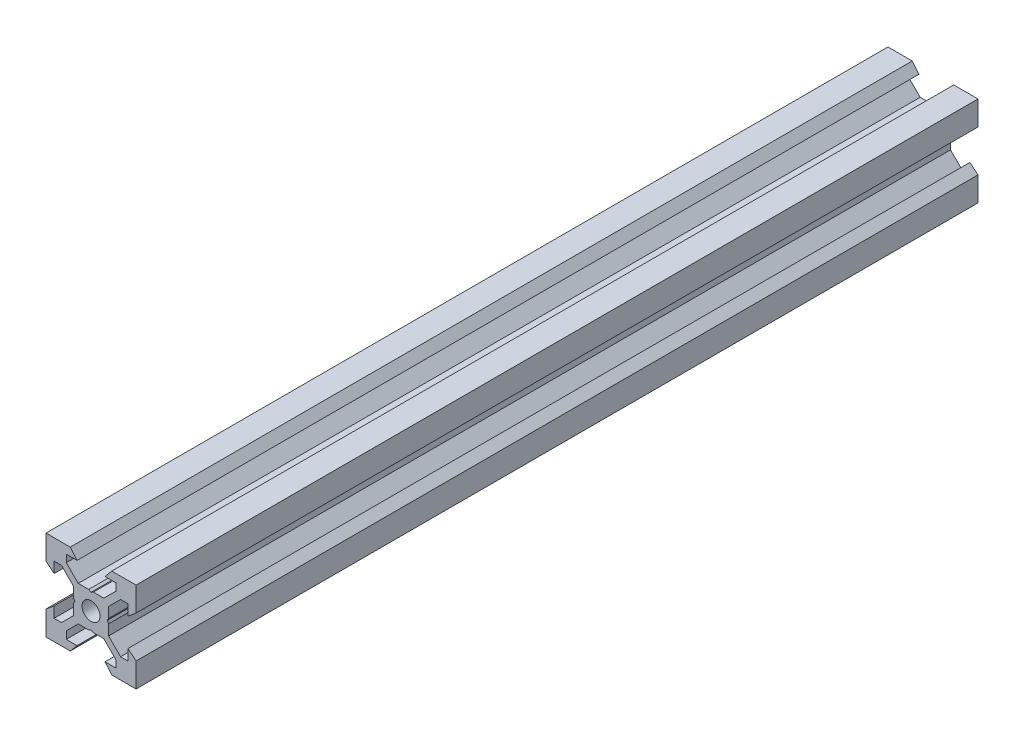
SolidWorks part; units mm, degrees
ref_plane "Front Plane" through (0, 0, 0) normal (0, 0, 1) x (1, 0, 0)
ref_plane "Top Plane" through (0, 0, 0) normal (0, 1, 0) x (1, 0, 0)
ref_plane "Right Plane" through (0, 0, 0) normal (1, 0, 0) x (0, 0, -1)
sketch "Sketch1" plane through (0, 0, 0) normal (0, 0, 1) x (1, 0, 0)
  line L0 (10, 10) -> (4.6104, 10) construction
  line L1 (10, 10) -> (10, 4.6104) construction
  line L2 (10, -10) -> (10, -4.6104) construction
  line L3 (10, -10) -> (4.6104, -10) construction
  line L4 (10, 10) -> (10, 4.6104)
  line L5 (6.5607, 5.5) -> (8.2, 5.5)
  line L6 (5.5, 8.2) -> (5.5, 6.5607)
  line L7 (10, 10) -> (4.6104, 10)
  line L8 (10, 10) -> (10, 4.6104)
  line L9 (6.5607, 5.5) -> (3.9, 2.8393)
  line L10 (5.5, 6.5607) -> (2.8393, 3.9)
  line L11 (10, 4.6104) -> (8.2, 3.1)
  line L12 (4.6104, 10) -> (3.1, 8.2)
  line L13 (8.2, 3.1) -> (8.2, 5.5)
  line L14 (3.1, 8.2) -> (5.5, 8.2)
  line L15 (-6.5607, 5.5) -> (-8.2, 5.5)
  line L16 (6.5607, -5.5) -> (8.2, -5.5)
  line L17 (3.1, -8.2) -> (5.5, -8.2)
  line L18 (8.2, -3.1) -> (8.2, -5.5)
  line L19 (4.6104, -10) -> (3.1, -8.2)
  line L20 (10, -4.6104) -> (8.2, -3.1)
  line L21 (0.5196, -3.9) -> (0, -3.6)
  line L22 (0.5196, 3.9) -> (0, 3.6)
  line L23 (3.6, 0) -> (3.9, -0.5196)
  line L24 (3.9, 0.5196) -> (3.6, 0)
  line L25 (3.9, 0.5196) -> (3.9, 2.8393)
  line L26 (2.8393, 3.9) -> (0.5196, 3.9)
  line L27 (3.9, -2.8393) -> (3.9, -0.5196)
  line L28 (2.8393, -3.9) -> (0.5196, -3.9)
  line L29 (5.5, -6.5607) -> (2.8393, -3.9)
  line L30 (6.5607, -5.5) -> (3.9, -2.8393)
  line L31 (10, -10) -> (10, -4.6104)
  line L32 (10, -10) -> (4.6104, -10)
  line L33 (5.5, -8.2) -> (5.5, -6.5607)
  line L34 (-6.5607, -5.5) -> (-8.2, -5.5)
  line L35 (10, -10) -> (10, -4.6104)
  line L36 (0, 0) -> (0, 8.2) construction
  line L37 (-10, -10) -> (-4.6104, -10) construction
  line L38 (-10, -10) -> (-10, -4.6104) construction
  line L39 (-10, 10) -> (-10, 4.6104) construction
  line L40 (-10, 10) -> (-4.6104, 10) construction
  line L41 (-10, -10) -> (-10, -4.6104)
  line L43 (-5.5, -8.2) -> (-5.5, -6.5607)
  line L44 (-10, -10) -> (-4.6104, -10)
  line L45 (-10, -10) -> (-10, -4.6104)
  line L46 (-6.5607, -5.5) -> (-3.9, -2.8393)
  line L47 (-5.5, -6.5607) -> (-2.8393, -3.9)
  line L48 (-2.8393, -3.9) -> (-0.5196, -3.9)
  line L49 (-3.9, -2.8393) -> (-3.9, -0.5196)
  line L50 (-2.8393, 3.9) -> (-0.5196, 3.9)
  line L51 (-3.9, 0.5196) -> (-3.9, 2.8393)
  line L52 (-3.9, 0.5196) -> (-3.6, 0)
  line L53 (-3.6, 0) -> (-3.9, -0.5196)
  line L54 (-0.5196, 3.9) -> (0, 3.6)
  line L55 (-0.5196, -3.9) -> (0, -3.6)
  line L56 (-10, -4.6104) -> (-8.2, -3.1)
  line L57 (-4.6104, -10) -> (-3.1, -8.2)
  line L58 (-8.2, -3.1) -> (-8.2, -5.5)
  line L59 (-3.1, -8.2) -> (-5.5, -8.2)
  line L60 (-10, -10) -> (10, -10) construction
  line L61 (-10, -10) -> (-10, 10) construction
  line L62 (-3.1, 8.2) -> (-5.5, 8.2)
  line L63 (-8.2, 3.1) -> (-8.2, 5.5)
  line L64 (-4.6104, 10) -> (-3.1, 8.2)
  line L65 (-10, 4.6104) -> (-8.2, 3.1)
  line L66 (-5.5, 6.5607) -> (-2.8393, 3.9)
  line L67 (-6.5607, 5.5) -> (-3.9, 2.8393)
  line L68 (-10, 10) -> (-10, 4.6104)
  line L69 (-10, 10) -> (-4.6104, 10)
  line L70 (-5.5, 8.2) -> (-5.5, 6.5607)
  line L71 (-10, 10) -> (10, 10) construction
  line L72 (-10, 10) -> (-10, 4.6104)
  line L73 (10, -10) -> (10, 10) construction
  line L74 (-10, -10) -> (10, 10) construction
  line L75 (-10, 10) -> (10, -10) construction
  circle A0 centre (0, 0) radius 2
  dimension "D7" = 4
  dimension "D1" = 20
  dimension "D2" = 5.3896
  dimension "D3" = 4.5
  dimension "D4" = 50
  dimension "D5" = 1.8
  dimension "D6" = 1.5104
  dimension "D8" = 5.5
  dimension "D9" = 120
  dimension "D10" = 0.3
  dimension "D11" = 2.3197
  dimension "D12" = 7.8
  dimension "D13" = 7.8
  dimension "D14" = 1.5
  dimension "D15" = 2.6607
extrude "Boss-Extrude1" add sketch "Sketch1" along normal mid plane 187 contours L70 L62 L64 L69 L68 L65 L63 L15 L67 L51 L52 L53 L49 L46 L34 L58 L56 L41 L44 L57 L59 L43 L47 L48 L55 L21 L28 L29 L33 L17 L19 L32 L31 L20 L18 L16 L30 L27 L23 L24 L25 L9 L5 L13 L11 L4 L7 L12 L14 L6 L10 region at (9.7172, 7.3052, 0)
